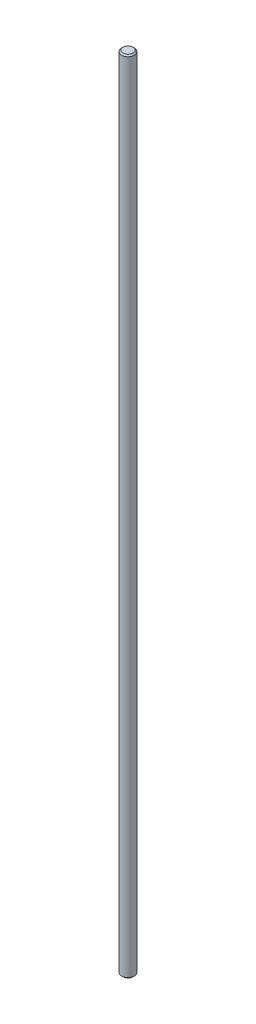
SolidWorks part; units mm, degrees
ref_plane "Front" through (0, 0, 0) normal (0, 0, 1) x (1, 0, 0)
ref_plane "Top" through (0, 0, 0) normal (0, 1, 0) x (1, 0, 0)
ref_plane "Right" through (0, 0, 0) normal (1, 0, 0) x (0, 0, -1)
sketch "Sketch1" plane through (0, 0, 0) normal (0, 1, 0) x (1, 0, 0)
  circle A0 centre (0, 0) radius 2.5
  dimension "D1" = 5
extrude "Boss-Extrude1" add sketch "Sketch1" along normal mid plane 315
chamfer "Chamfer1" distance 0.5 angle 45 2 edges at (0, -157.5, 2.5) (0, 157.5, 2.5)
ref_axis "Axis1" through (0, 156.1806, 0) along (0, -1, 0)
